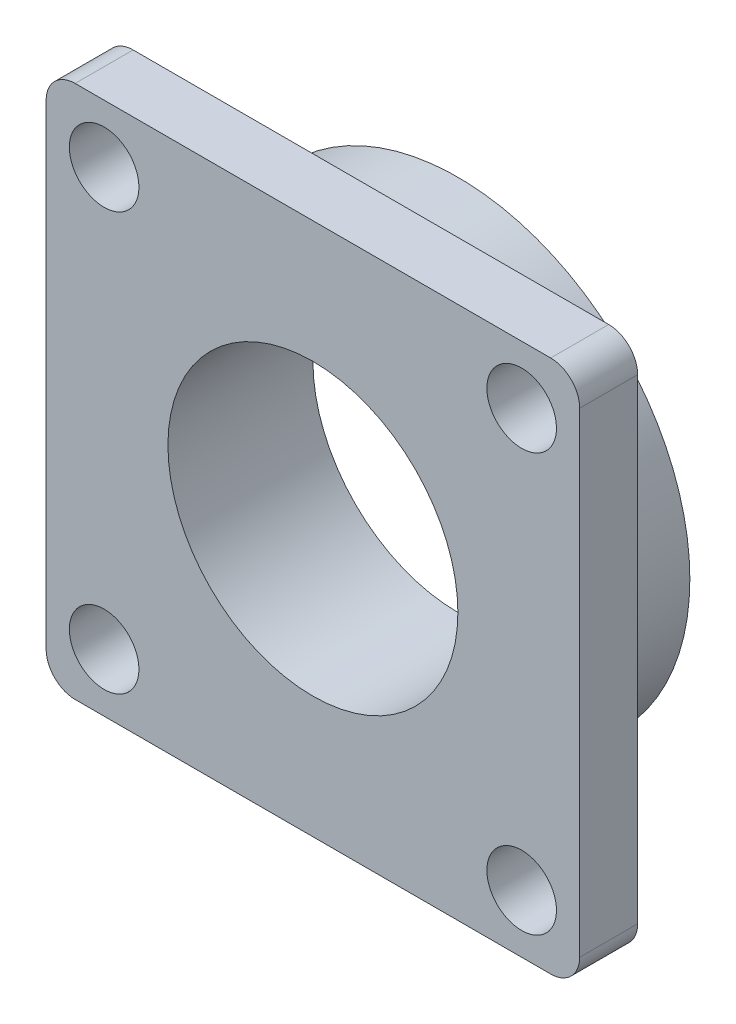
SolidWorks part; units mm, degrees
ref_plane "Plan de face" through (0, 0, 0) normal (0, 0, 1) x (1, 0, 0)
ref_plane "Plan de dessus" through (0, 0, 0) normal (0, 1, 0) x (1, 0, 0)
ref_plane "Plan de droite" through (0, 0, 0) normal (1, 0, 0) x (0, 0, -1)
sketch "Esquisse1" plane through (0, 0, 0) normal (0, 0, 1) x (1, 0, 0)
  circle A0 centre (0, 0) radius 25
  circle A1 centre (0, 0) radius 40
  dimension "D1" = 50
  dimension "D2" = 80
extrude "Boss.-Extru.1" add sketch "Esquisse1" along normal blind 25
sketch "Esquisse3" plane through (0, 0, 0) normal (0, 0, -1) x (-1, 0, 0)
  line L0 (90, 0) -> (-90, 0) construction
  line L1 (79.2726, 0) -> (108.9029, 0) construction
  line L2 (16.9047, -36.2523) -> (95.8264, -19.1325)
  line L3 (16.9047, 36.2523) -> (95.8264, 19.1325)
  line L4 (-16.9047, 36.2523) -> (-95.8264, 19.1325)
  line L5 (0, 0) -> (0, 35.0453) construction
  line L6 (0, 0) -> (-17.2687, 37.0328) construction
  line L7 (0, 0) -> (17.2687, 37.0328) construction
  line L9 (-79.2726, 0) -> (-108.9029, 0) construction
  line L11 (-16.9047, -36.2523) -> (-95.8264, -19.1325)
  arc A0 (95.8264, 19.1325) -> (95.8264, -19.1325) centre (90, 0) cw
  circle A1 centre (-90, 0) radius 8
  arc A2 (-95.8264, 19.1325) -> (-95.8264, -19.1325) centre (-90, 0) ccw
  circle A3 centre (90, 0) radius 8
  circle A4 centre (0, 0) radius 40 construction
  arc A5 (16.9047, 36.2523) -> (-16.9047, 36.2523) centre (0, 0) ccw
  arc A6 (-16.9047, -36.2523) -> (16.9047, -36.2523) centre (0, 0) ccw
  circle A7 centre (0, 0) radius 32
  dimension "D3" = 16
  dimension "D5" = 64
  dimension "D6" = 20
  dimension "D2" = 25
  dimension "D4" = 90
sketch "Esquisse4" plane through (0, 0, 25) normal (0, 0, 1) x (1, 0, 0)
  line L0 (0, 0) -> (0, 23.3521) construction
  line L1 (41, 46) -> (-41, 46)
  line L2 (46, 41) -> (46, -41)
  line L3 (41, -46) -> (-41, -46)
  line L4 (-46, 41) -> (-46, -41)
  arc A0 (-46, -41) -> (-41, -46) centre (-41, -41) ccw
  arc A1 (41, -46) -> (46, -41) centre (41, -41) ccw
  arc A2 (46, 41) -> (41, 46) centre (41, 41) ccw
  arc A3 (-41, 46) -> (-46, 41) centre (-41, 41) ccw
  circle A4 centre (-36, 36) radius 6
  circle A5 centre (-36, -36) radius 6
  circle A6 centre (36, -36) radius 6
  circle A7 centre (36, 36) radius 6
  circle A8 centre (0, 0) radius 25
  point P7 (-46, -46)
  point P12 (46, 46)
  point P15 (-46, 46)
  dimension "D5" = 5
  dimension "D6" = 12
  dimension "D7" = 12
  dimension "D8" = 10
  dimension "D12" = 50
  dimension "D1" = 92
  dimension "D2" = 92
  dimension "D3" = 46
  dimension "D4" = 46
  dimension "D9" = 10
  dimension "D10" = 10
  dimension "D11" = 10
extrude "Boss.-Extru.2" add sketch "Esquisse4" against normal blind 10
fillet "Congé1" radius 5 1 edges at (40, 0, 15)
sketch "Esquisse5" plane through (0, 46, 0) normal (0, 1, 0) x (1, 0, 0)
  line L0 (0, -15) -> (0, -25) construction
  line L1 (41, -15) -> (-41, -15) construction
  line L2 (41, -25) -> (-41, -25) construction
sketch "Esquisse6" plane through (46, 0, 0) normal (1, 0, 0) x (0, 0, -1)
  line L0 (-15, 0) -> (-25, 0) construction
  line L1 (-15, -41) -> (-15, 41) construction
  line L2 (-25, -41) -> (-25, 41) construction
sketch "Esquisse7" plane through (0, -46, 0) normal (0, -1, 0) x (1, 0, 0)
  line L0 (0, 15) -> (0, 25) construction
sketch "Esquisse8" plane through (-46, 0, 0) normal (-1, 0, 0) x (0, 0, 1)
  line L0 (15, 0) -> (25, 0) construction
  line L1 (15, 41) -> (15, -41) construction
  line L2 (25, 41) -> (25, -41) construction
